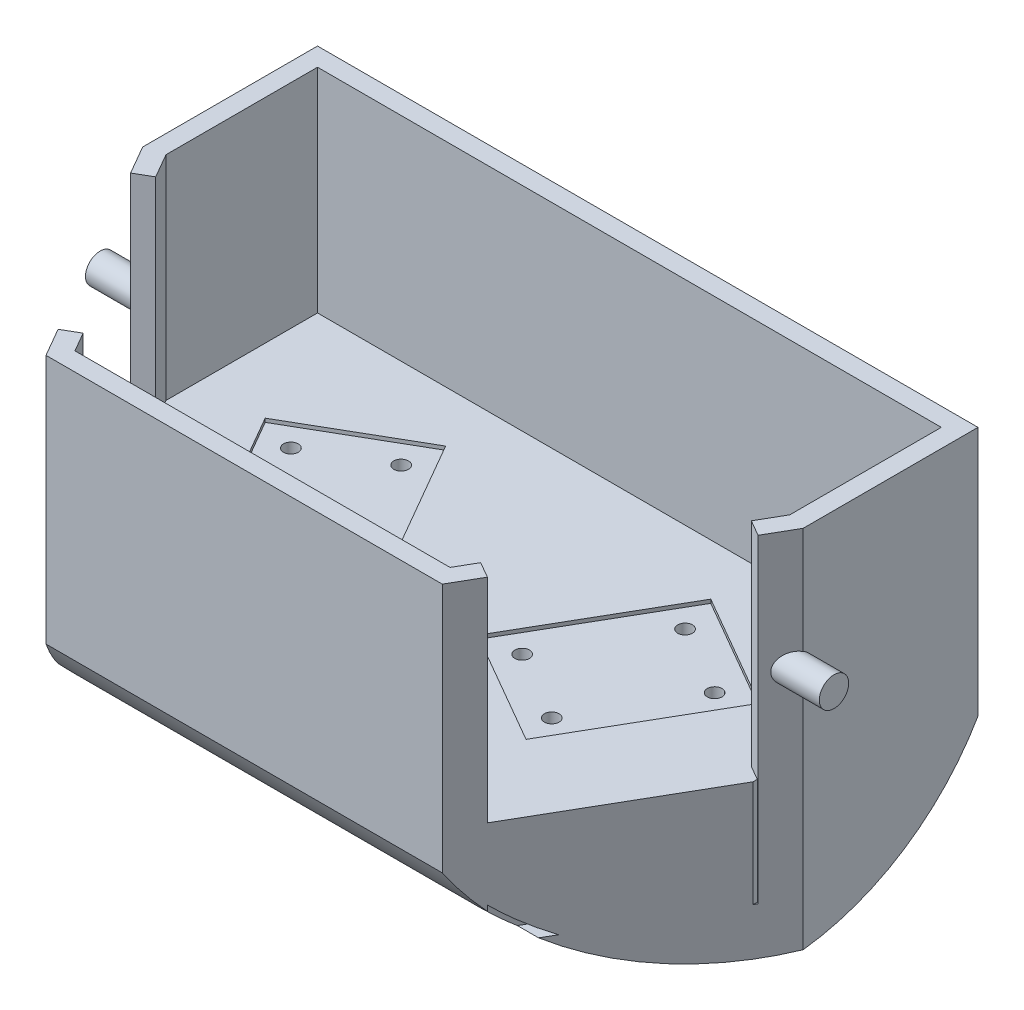
SolidWorks part; units mm, degrees
ref_plane "Front Plane" through (0, 0, 0) normal (0, 0, 1) x (1, 0, 0)
ref_plane "Top Plane" through (0, 0, 0) normal (0, 1, 0) x (1, 0, 0)
ref_plane "Right Plane" through (0, 0, 0) normal (1, 0, 0) x (0, 0, -1)
sketch "Sketch2" plane through (0, 0, 0) normal (0, 1, 0) x (1, 0, 0)
  line L0 (-54, -55) -> (-90, 7.3538)
  line L1 (-90, -55) -> (90, -55)
  line L2 (-90, -55) -> (-90, 55)
  line L3 (-90, 55) -> (90, 55)
  line L4 (90, -55) -> (90, 55)
  line L5 (-90, -55) -> (90, 55) construction
  line L6 (-90, 55) -> (90, -55) construction
  line L7 (0, -55) -> (0, 55) construction
  line L8 (54, -55) -> (90, 7.3538)
  point P0 (0, 0)
  dimension "D1" = 110
  dimension "D2" = 180
  dimension "D3" = 72
  dimension "D4" = 30
extrude "Boss-Extrude1" add sketch "Sketch2" along normal blind 50 and the other way blind 50 contours L1 L8 L4 L3 L2 L0 region at (0, 0, -4.375)
sketch "Sketch13" plane through (-90, 0, 0) normal (-1, 0, 0) x (0, 0, 1)
  line L0 (55, -50) -> (55, 50) construction
  line L1 (-55, -50) -> (55, -50)
  line L2 (-55, -50) -> (-55, -18.1472)
  line L3 (-55, -18.1472) -> (55, -18.1472)
  line L4 (55, -50) -> (55, -18.1472)
  line L5 (-55, -18.1472) -> (-55, -50)
  line L6 (-55, -50) -> (55, -50)
  line L7 (55, -50) -> (55, -18.1472)
  arc A1 (-55, -18.1472) -> (55, -18.1472) centre (0, 13.61) ccw
  point P8 (0, -49.9)
  line M1 (-7.3538, -50) -> (-7.3538, 50)
  line M3 (-55, 50) -> (-55, -50)
  line M4 (-55, -50) -> (-7.3538, -50)
  dimension "D1" = 63.51
  dimension "D2" = 0.1
extrude "Cut-Extrude9" cut sketch "Sketch13" against normal up to next contours A1 M3 M4 M1 | A1 L1 L4 M1 region at (-90, -41.0554, -42.0031) region at (-90, -41.1161, 41.7126)
shell "Shell1" thickness 5 removed face at (0, 50, -2.4513)
sketch "Sketch5" plane through (-64.3157, 0, 37.1327) normal (-0.866, 0, 0.5) x (0.5, 0, 0.866)
  line L0 (20.6314, 50) -> (-51.3686, 50) construction
  line L1 (-42.3686, 50) -> (11.6314, 50)
  line L2 (-42.3686, 50) -> (-42.3686, -37)
  line L3 (-42.3686, -37) -> (11.6314, -37)
  line L4 (11.6314, 50) -> (11.6314, -37)
  line L6 (20.6314, -18.1472) -> (20.6314, 50) construction
  dimension "D1" = 87
  dimension "D2" = 54
  dimension "D3" = 9
extrude "Cut-Extrude2" cut sketch "Sketch5" against normal blind 5
mirror "Mirror1" about plane through (0, 0, 0) normal (1, 0, 0) of "Cut-Extrude2"
sketch "Sketch16" plane through (-85, 0, 0) normal (1, 0, 0) x (0, 0, -1)
  line L0 (-55, -8) -> (55, -8)
  line L1 (-55, -18.1472) -> (-55, 50) construction
  line L2 (55, -18.1472) -> (55, 50) construction
  line L3 (-55, -8) -> (-55, -18.1472)
  line L4 (55, -8) -> (55, -18.1472)
  line L5 (7.3538, 50) -> (55, 50) construction
  arc A0 (-55, -18.1472) -> (55, -18.1472) centre (0, 20.3642) ccw
  dimension "D1" = 58
extrude "Boss-Extrude4" add sketch "Sketch16" along normal up to surface (170 mm away) up to face at (85, 8.5943, -30.1107)
sketch "Sketch6" plane through (0, -8, 0) normal (0, 1, 0) x (1, 0, 0)
  line L0 (-36.1276, 36.0441) -> (-12.8776, -4.2261)
  line L1 (-36.1276, 36.0441) -> (-67.3045, 18.0441)
  line L2 (-12.8776, -4.2261) -> (-44.0545, -22.2261)
  line L3 (-67.3045, 18.0441) -> (-44.0545, -22.2261)
  line L6 (-51.1132, -50) -> (-54.1699, -44.7058) construction
  line L13 (-38.6898, 26.4819) -> (-22.4398, -1.6639)
  line L14 (-22.4398, -1.6639) -> (-41.4923, -12.6639)
  line L15 (-57.7423, 15.4819) -> (-41.4923, -12.6639)
  line L16 (-38.6898, 26.4819) -> (-57.7423, 15.4819)
  line L17 (0, -55) -> (0, 55) construction
  line L18 (12.8776, -4.2261) -> (44.0545, -22.2261)
  line L19 (67.3045, 18.0441) -> (44.0545, -22.2261)
  line L20 (36.1276, 36.0441) -> (67.3045, 18.0441)
  line L21 (36.1276, 36.0441) -> (12.8776, -4.2261)
  circle A8 centre (-57.7423, 15.4819) radius 2
  circle A9 centre (-38.6898, 26.4819) radius 2
  circle A10 centre (-41.4923, -12.6639) radius 2
  circle A11 centre (-22.4398, -1.6639) radius 2
  circle A12 centre (22.4398, -1.6639) radius 2
  circle A13 centre (41.4923, -12.6639) radius 2
  circle A14 centre (38.6898, 26.4819) radius 2
  circle A15 centre (57.7423, 15.4819) radius 2
  dimension "D4" = 7
  dimension "D5" = 4
  dimension "D6" = 4
  dimension "D7" = 4
  dimension "D9" = 4
  dimension "D1" = 20
  dimension "D2" = 46.5
  dimension "D3" = 36
  dimension "D8" = 0.75
extrude "Cut-Extrude4" cut sketch "Sketch6" against normal through all contours A8 | A9 | A10 | A11 | A12 | A14 | A15 | A13
extrude "Cut-Extrude5" cut sketch "Sketch6<4>" against normal blind 1 contours L20 L21 L18 L19 A14 A12 A13 A15 | L0 L1 L3 L2 region at (40.091, -8, -6.909)
sketch "Sketch6<4>" plane through (0, -8, 0) normal (0, 1, 0) x (1, 0, 0) same geometry as "Sketch6"
sketch "Sketch17" plane through (0, -8, 0) normal (0, 1, 0) x (1, 0, 0)
  line L0 (-54, -55) -> (-85, -55)
  line L1 (-54, -55) -> (-85, -55) construction
  line L2 (-85, -55) -> (-85, -1.3064)
  line L3 (-85, -1.3064) -> (-54, -55)
  line L4 (85, -55) -> (54, -55)
  line L5 (54, -55) -> (85, -1.3064)
  line L6 (85, -1.3064) -> (85, -55)
extrude "Cut-Extrude10" cut sketch "Sketch17" against normal up to next
sketch "Sketch18" plane through (-90, 0, 0) normal (-1, 0, 0) x (0, 0, 1)
  line L0 (55, -18.1472) -> (55, 50) construction
  arc A0 (-55, -18.1472) -> (55, -18.1472) centre (0, 17.2426) ccw
  circle A1 centre (-5.7558, 17.2426) radius 4
  dimension "D1" = 8
extrude "Boss-Extrude5" add sketch "Sketch18" along normal blind 10 and the other way up to body contours A1
mirror "Mirror2" about plane through (0, 0, 0) normal (1, 0, 0) of "Boss-Extrude5"
